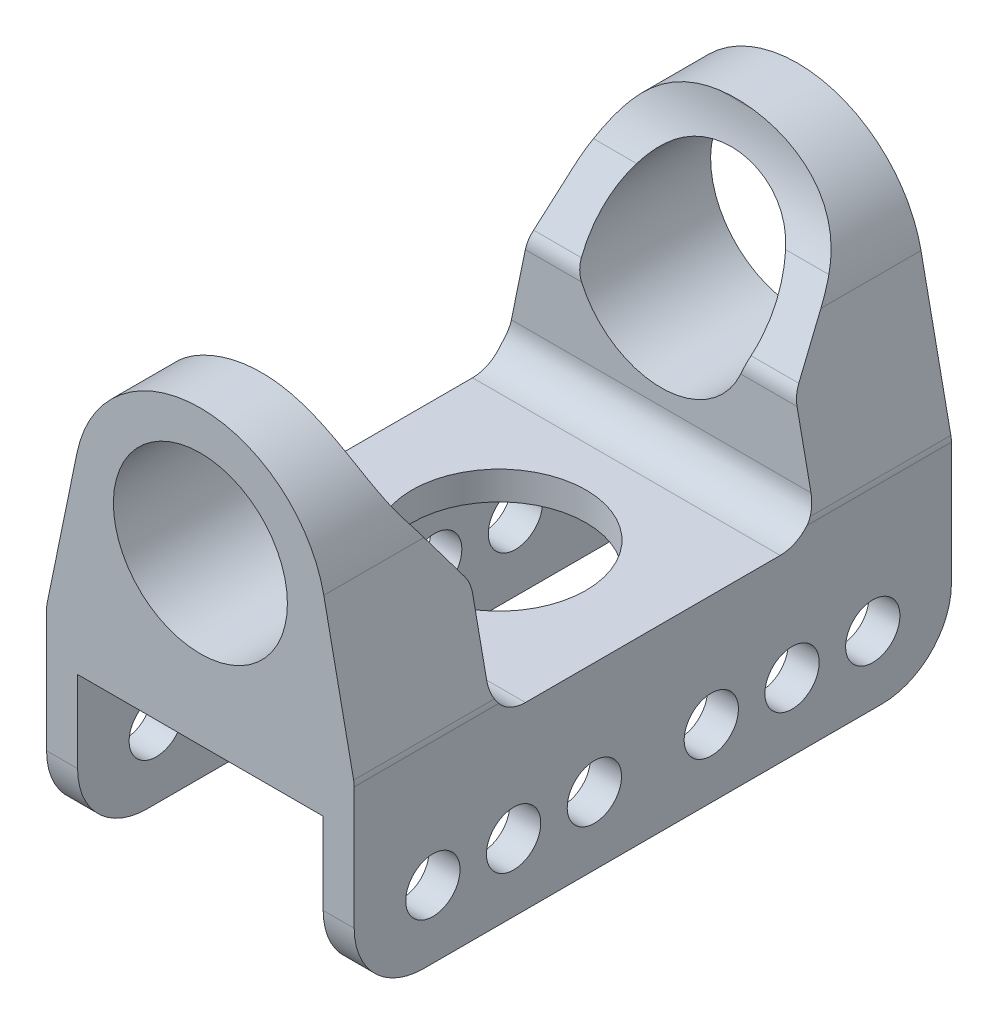
SolidWorks part; units mm, degrees
material "6061-T6 (SS)"
ref_plane "Front" through (0, 0, 0) normal (0, 0, 1) x (1, 0, 0)
ref_plane "Top" through (0, 0, 0) normal (0, 1, 0) x (1, 0, 0)
ref_plane "Right" through (0, 0, 0) normal (1, 0, 0) x (0, 0, -1)
sketch "Sketch1" plane through (0, 0, 0) normal (0, 0, 1) x (1, 0, 0)
  line L0 (0, 0) -> (0, -15.1638) construction
  line L1 (11.2577, 2.3161) -> (14.0335, -11.176)
  line L2 (14.0335, -11.176) -> (14.0335, -28.956)
  line L3 (14.0335, -28.956) -> (11.2014, -28.956)
  line L4 (11.2014, -28.956) -> (11.2014, -15.1638)
  line L5 (11.2014, -15.1638) -> (-11.2014, -15.1638)
  line L6 (-11.2014, -15.1638) -> (-11.2014, -28.956)
  line L7 (-11.2014, -28.956) -> (-14.0335, -28.956)
  line L8 (-14.0335, -28.956) -> (-14.0335, -11.176)
  line L9 (-14.0335, -11.176) -> (-11.2577, 2.3161)
  line L10 (-14.0335, -11.176) -> (14.0335, -11.176) construction
  line L11 (-11.2014, -28.956) -> (11.2014, -28.956) construction
  circle A0 centre (0, 0) radius 7.9375
  arc A1 (11.2577, 2.3161) -> (-11.2577, 2.3161) centre (0, 0) ccw
  point P4 (0, 11.4935)
  dimension "D1" = 15.875
  dimension "D4" = 3.556
  dimension "D2" = 22.4028
  dimension "D3" = 13.7922
  dimension "D5" = 28.956
  dimension "D6" = 28.067
  dimension "D7" = 17.78
extrude "Boss-Extrude1" add sketch "Sketch1" along normal mid plane 54.483
sketch "Sketch2" plane through (14.0335, 0, 0) normal (1, 0, 0) x (0, 0, -1)
  line L0 (-20.066, -22.7838) -> (20.066, -22.7838) construction
  line L3 (0, -28.956) -> (0, -11.176) construction
  line L4 (-27.2415, -28.956) -> (27.2415, -28.956) construction
  line L5 (-27.2415, -11.176) -> (27.2415, -11.176) construction
  line L6 (-27.2415, -15.1638) -> (27.2415, -15.1638) construction
  line L7 (-27.2415, -15.1638) -> (27.2415, -15.1638) construction
  circle A0 centre (-20.066, -22.7838) radius 2.4765
  circle A1 centre (-12.7, -22.7838) radius 2.4765
  circle A2 centre (-5.334, -22.7838) radius 2.4765
  circle A3 centre (5.334, -22.7838) radius 2.4765
  circle A4 centre (12.7, -22.7838) radius 2.4765
  circle A5 centre (20.066, -22.7838) radius 2.4765
  point P2 (0, -22.7838)
  dimension "D1" = 4.953
  dimension "D2" = 25.4
  dimension "D3" = 7.366
  dimension "D4" = 7.366
  dimension "D5" = 7.366
  dimension "D6" = 7.366
  dimension "D7" = 7.62
extrude "Cut-Extrude1" cut sketch "Sketch2" against normal through all
sketch "Sketch3" plane through (14.0335, 0, 0) normal (1, 0, 0) x (0, 0, -1)
  line L4 (-14.7955, -2.413) -> (14.7955, -2.413) construction
  line L5 (-21.6535, 7.3812) -> (21.6535, 7.3812) construction
  line L7 (14.7955, -12.573) -> (-14.7955, -12.573)
  line L8 (-27.2415, -28.956) -> (27.2415, -28.956) construction
  line L9 (0, -12.573) -> (0, 11.4935)
  line L10 (14.7955, -12.573) -> (14.7955, -2.413)
  line L11 (14.7955, -2.413) -> (21.6535, 7.3812)
  line L12 (21.6535, 7.3812) -> (21.6535, 11.4935)
  line L13 (27.2415, 11.4935) -> (-27.2415, 11.4935) construction
  line L14 (-14.7955, -12.573) -> (-14.7955, -2.413)
  line L15 (-14.7955, -2.413) -> (-21.6535, 7.3812)
  line L16 (-21.6535, 7.3812) -> (-21.6535, 11.4935)
  line L17 (-21.6535, 11.4935) -> (21.6535, 11.4935)
  line L18 (27.2415, 11.4935) -> (-27.2415, 11.4935) construction
  dimension "D1" = 16.383
  dimension "D2" = 29.591
  dimension "D3" = 5.588
  dimension "D4" = 125
  dimension "D5" = 10.16
extrude "Cut-Extrude2" cut sketch "Sketch3" against normal through all contours L15 L16 L17 L12 L11 L10 L7 L14
sketch "Sketch4" plane through (0, -15.1638, 0) normal (0, -1, 0) x (1, 0, 0)
  circle A0 centre (0, 0) radius 7.9375
  dimension "D1" = 15.875
extrude "Cut-Extrude3" cut sketch "Sketch4" against normal through all
fillet "Fillet1" radius 6.35 4 edges at (12.6175, -28.956, -27.2415) (-12.6174, -28.956, -27.2415) (-12.6174, -28.956, 27.2415) (12.6175, -28.956, 27.2415)
fillet "Fillet2" radius 3.175 2 edges at (0, -12.573, 14.7955) (0, -12.573, -14.7955)
fillet "Fillet3" radius 12.7 2 edges at (5.8646, 7.3812, 21.6535) (5.8646, 7.3812, -21.6535)
fillet "Fillet4" radius 2.54 4 edges at (9.8962, -2.413, -14.7955) (-9.8962, -2.413, -14.7955) (-9.8962, -2.413, 14.7955) (9.8962, -2.413, 14.7955)
fillet "Fillet5" radius 2.54 4 edges at (-14.0335, -11.176, 20.7462) (-14.0335, -11.176, -20.7462) (14.0335, -11.176, -20.7462) (14.0335, -11.176, 20.7462)
